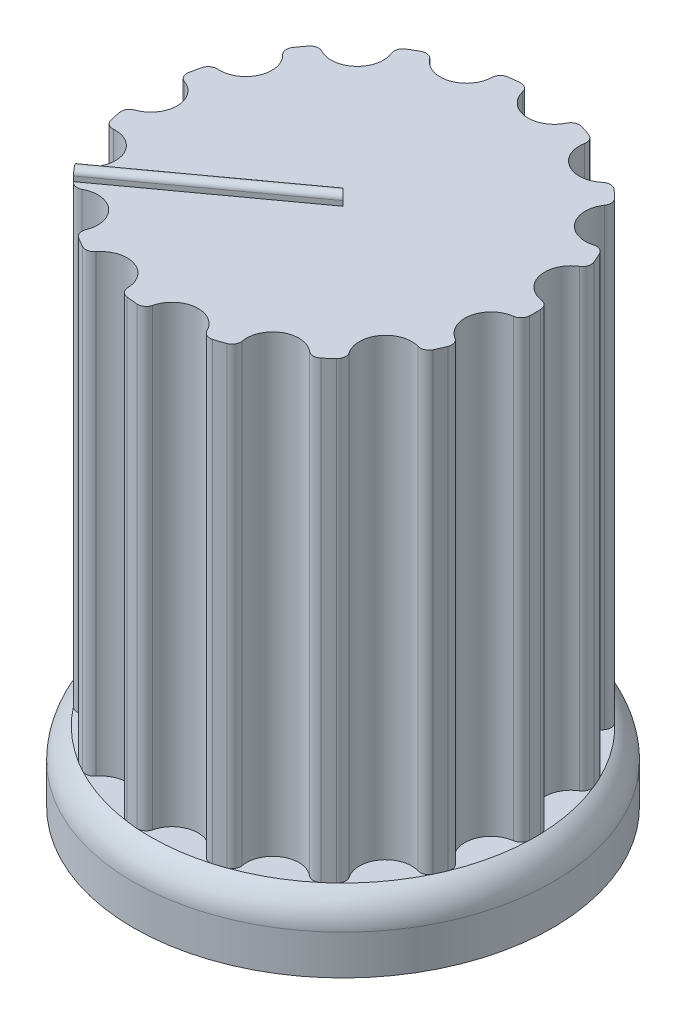
SolidWorks part; units mm, degrees
ref_plane "Front Plane" through (0, 0, 0) normal (0, 0, 1) x (1, 0, 0)
ref_plane "Top Plane" through (0, 0, 0) normal (0, 1, 0) x (1, 0, 0)
ref_plane "Right Plane" through (0, 0, 0) normal (1, 0, 0) x (0, 0, -1)
sketch "Sketch1" plane through (0, 0, 0) normal (0, 1, 0) x (1, 0, 0)
  circle A0 centre (0, 0) radius 6
extrude "Boss-Extrude1" add sketch "Sketch1" along normal blind 15
sketch "Sketch2" plane through (0, 15, 0) normal (0, 1, 0) x (1, 0, 0)
  circle A3 centre (0, 0) radius 5.5
  circle A4 centre (0, 0) radius 5.5
  circle M2 centre (0, 0) radius 6
  dimension "D1" = 0.5
extrude "Cut-Extrude1" cut sketch "Sketch2" against normal blind 13 contours A4 M2 region at (-5.8303, 15, 0)
fillet "Fillet1" radius 1 1 edges at (0, 2, 6)
sketch "Sketch3" plane through (0, 15, 0) normal (0, 1, 0) x (1, 0, 0)
  line L0 (-6.6, 0) -> (6.6, 0) construction
  circle A0 centre (-5.5, 0) radius 0.75
  circle A1 centre (0, 0) radius 5.5 construction
extrude "Cut-Extrude2" cut sketch "Sketch3" against normal blind 13
fillet "Fillet2" radius 0.25 2 edges at (-5.4489, 8.5, 0.7483) (-5.4489, 8.5, -0.7483)
pattern_circular "CirPattern1" count 15 every 24 about axis through (0, 15, 0) along (0, 1, 0) of "Cut-Extrude2", "Fillet2"
sketch "Sketch4" plane through (0, 0, 0) normal (0, -1, 0) x (1, 0, 0)
  line L1 (0, 0) -> (4.9165, -2.8385)
  line L2 (4.9165, -2.8385) -> (0, 0)
  line L3 (0, 0) -> (7.9027, 0)
  line L4 (6.6, 0) -> (-6.6, 0) construction
  circle A0 centre (0, 0) radius 3.5
  dimension "D1" = 30
extrude "Cut-Extrude3" cut sketch "Sketch4" against normal blind 14 contours A0
sketch "Sketch5" plane through (0, 14, 0) normal (0, -1, 0) x (1, 0, 0)
  line L0 (0, 0) -> (3.1302, 0)
  line L1 (6.6, 0) -> (-6.6, 0) construction
  line L2 (3.1302, 0) -> (0, 0)
  line L3 (0, 0) -> (2.2365, -1.2912)
  line L4 (4.473, -2.5825) -> (0, 0)
  line L5 (4.348, -2.799) -> (4.598, -2.366)
  line L6 (-4.473, 2.5825) -> (4.473, -2.5825)
  line L7 (4.598, -2.366) -> (-4.348, 2.799)
  line L8 (4.348, -2.799) -> (-4.598, 2.366)
  line L9 (-4.598, 2.366) -> (-4.348, 2.799)
  line L10 (-3.9967, 2.0188) -> (-3.7467, 2.4518)
  line L11 (-3.7467, 2.4518) -> (3.4065, -1.678)
  line L12 (3.4065, -1.678) -> (3.1565, -2.1111)
  point P9 (2.2365, -1.2912)
  point P11 (4.473, -2.5825)
  point P14 (0, 0)
  circle M8 centre (0, 0) radius 3.5
  dimension "D1" = 30
  dimension "D2" = 0.5
extrude "Boss-Extrude2" add sketch "Sketch5" along normal blind 7 contours L7 L0 L3 L4 M8 | L8 L4 L3 L6 M8 | L0 L7 L6 M8 region at (-1.355, 14, 0.9294) region at (1.667, 14, -0.8214) region at (-0.0625, 14, -0.1082)
fillet "Fillet3" radius 0.25 2 edges at (0.125, 14, 0.2165) (-0.125, 14, -0.2165)
sketch "Sketch6" plane through (0, 15, 0) normal (0, 1, 0) x (1, 0, 0)
  line L0 (-4.354, -3.3605) -> (-4.5415, -3.1024)
  line L1 (-4.5415, -3.1024) -> (-0.1142, 0.1142)
  line L2 (-0.1142, 0.1142) -> (0, 0)
  line L3 (0, 0) -> (0.1142, -0.1142)
  line L4 (0.1142, -0.1142) -> (-4.354, -3.3605)
extrude "Boss-Extrude3" add sketch "Sketch6" along normal blind 0.3
fillet "Fillet4" 2 edges at (-2.1199, 15.3, 1.7373) (-2.3279, 15.3, 1.4941) type full round first side face at (-2.6784, 15.1875, 2.1431) second side face at (-1.7745, 15.1875, 1.092) middle face at (-2.2239, 15.3, 1.6157)
